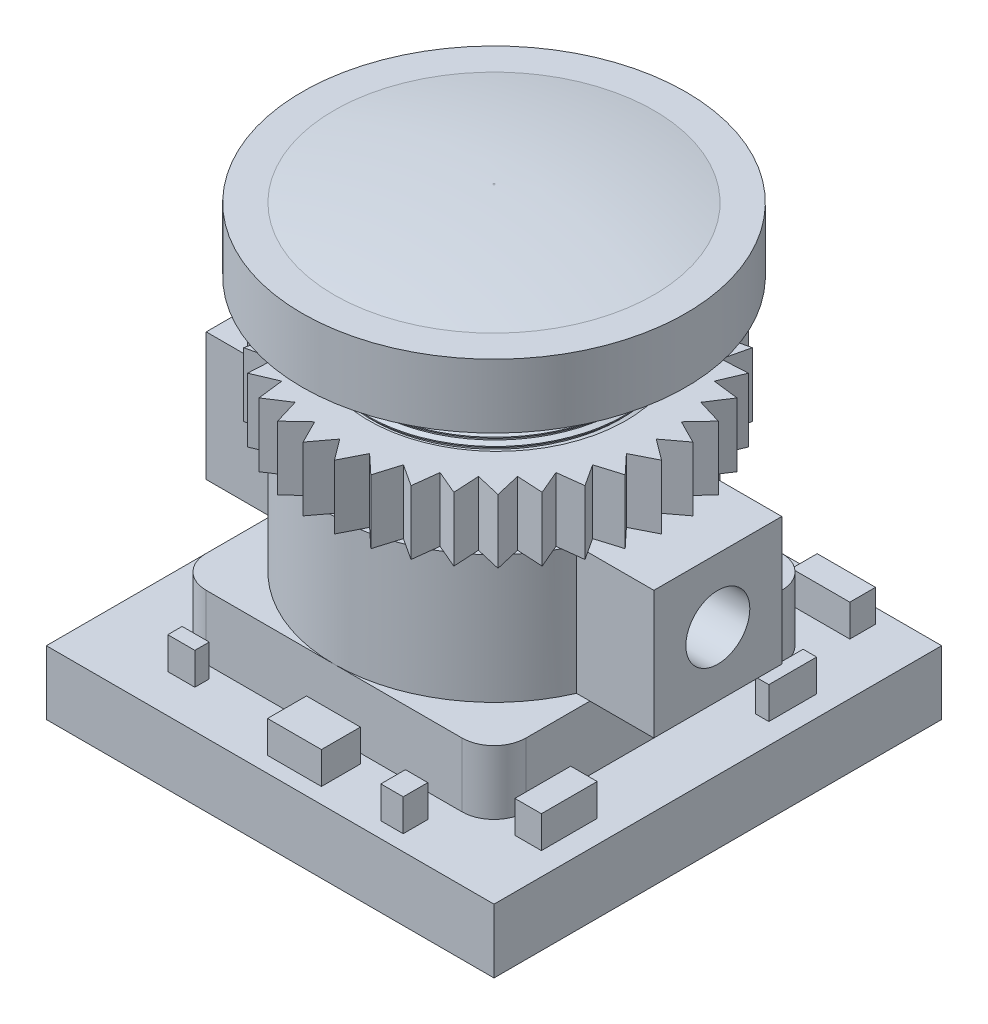
SolidWorks part; units mm, degrees
ref_plane "Front Plane" through (0, 0, 0) normal (0, 0, 1) x (1, 0, 0)
ref_plane "Top Plane" through (0, 0, 0) normal (0, 1, 0) x (1, 0, 0)
ref_plane "Right Plane" through (0, 0, 0) normal (1, 0, 0) x (0, 0, -1)
sketch "Sketch1" plane through (0, 0, 0) normal (0, 1, 0) x (1, 0, 0)
  line L1 (0, 0) -> (14, 0)
  line L2 (0, 0) -> (0, 14)
  line L3 (0, 14) -> (14, 14)
  line L4 (14, 0) -> (14, 14)
  dimension "D1" = 14
  dimension "D2" = 14
extrude "Boss-Extrude1" add sketch "Sketch1" along normal blind 2
sketch "Sketch2" plane through (0, 2, 0) normal (0, 1, 0) x (1, 0, 0)
  line L0 (0, 0) -> (14, 0) construction
  line L1 (2, 2) -> (12, 2)
  line L2 (2, 2) -> (2, 12)
  line L3 (2, 12) -> (12, 12)
  line L4 (12, 2) -> (12, 12)
  line L5 (2.4541, 13.3046) -> (3.448, 13.3046)
  line L6 (2.4541, 13.3046) -> (2.4541, 12.7429)
  line L7 (2.4541, 12.7429) -> (3.448, 12.7429)
  line L8 (3.448, 13.3046) -> (3.448, 12.7429)
  line L9 (12.3842, 12.7429) -> (10.5607, 12.7429)
  line L10 (12.3842, 12.7429) -> (12.3842, 13.5466)
  line L11 (12.3842, 13.5466) -> (10.5607, 13.5466)
  line L12 (10.5607, 12.7429) -> (10.5607, 13.5466)
  line L13 (12.9287, 10.7378) -> (13.3521, 10.7378)
  line L14 (12.9287, 10.7378) -> (12.9287, 9.2427)
  line L15 (12.9287, 9.2427) -> (13.3521, 9.2427)
  line L16 (13.3521, 10.7378) -> (13.3521, 9.2427)
  line L21 (13.2916, 2.1905) -> (12.462, 2.1905)
  line L22 (13.2916, 2.1905) -> (13.2916, 3.9363)
  line L23 (13.2916, 3.9363) -> (12.462, 3.9363)
  line L24 (12.462, 2.1905) -> (12.462, 3.9363)
  line L25 (9.973, 1.2571) -> (10.673, 1.2571)
  line L26 (9.973, 1.2571) -> (9.973, 0.488)
  line L27 (9.973, 0.488) -> (10.673, 0.488)
  line L28 (10.673, 1.2571) -> (10.673, 0.488)
  line L29 (8.1149, 0.488) -> (6.4296, 0.488)
  line L30 (8.1149, 0.488) -> (8.1149, 1.7066)
  line L31 (8.1149, 1.7066) -> (6.4296, 1.7066)
  line L32 (6.4296, 0.488) -> (6.4296, 1.7066)
  line L33 (3.448, 1.1967) -> (2.601, 1.1967)
  line L34 (3.448, 1.1967) -> (3.448, 1.6461)
  line L35 (3.448, 1.6461) -> (2.601, 1.6461)
  line L36 (2.601, 1.1967) -> (2.601, 1.6461)
  line L37 (1.0108, 5.0425) -> (1.3133, 5.0425)
  line L38 (1.0108, 5.0425) -> (1.0108, 3.7894)
  line L39 (1.0108, 3.7894) -> (1.3133, 3.7894)
  line L40 (1.3133, 5.0425) -> (1.3133, 3.7894)
  line L41 (1.659, 6.4166) -> (0.6824, 6.4166)
  line L42 (1.659, 6.4166) -> (1.659, 7.7303)
  line L43 (1.659, 7.7303) -> (0.6824, 7.7303)
  line L44 (0.6824, 6.4166) -> (0.6824, 7.7303)
  line L45 (0.9503, 10.7378) -> (1.659, 10.7378)
  line L46 (0.9503, 10.7378) -> (0.9503, 9.8736)
  line L47 (0.9503, 9.8736) -> (1.659, 9.8736)
  line L48 (1.659, 10.7378) -> (1.659, 9.8736)
  line L49 (1.4948, 12.0428) -> (0.838, 12.0428)
  line L50 (1.4948, 12.0428) -> (1.4948, 12.7429)
  line L51 (1.4948, 12.7429) -> (0.838, 12.7429)
  line L52 (0.838, 12.0428) -> (0.838, 12.7429)
  line L53 (5.8333, 13.0799) -> (6.1444, 13.0799)
  line L54 (5.8333, 13.0799) -> (5.8333, 12.5268)
  line L55 (5.8333, 12.5268) -> (6.1444, 12.5268)
  line L56 (6.1444, 13.0799) -> (6.1444, 12.5268)
  line L57 (8.2704, 12.1811) -> (6.7321, 12.1811)
  line L58 (8.2704, 12.1811) -> (8.2704, 13.7626)
  line L59 (8.2704, 13.7626) -> (6.7321, 13.7626)
  line L60 (6.7321, 12.1811) -> (6.7321, 13.7626)
  dimension "D1" = 10
  dimension "D2" = 10
  dimension "D3" = 2
  dimension "D5" = 1.3136
extrude "Boss-Extrude3" add sketch "Sketch2" along normal blind 2 contours L2 L1 L4 L3
fillet "Fillet1" radius 1 1 edges at (2, 3, -2)
fillet "Fillet2" radius 1 3 edges at (12, 3, -2) (12, 3, -12) (2, 3, -12)
sketch "Sketch4" plane through (0, 2, 0) normal (0, 1, 0) x (1, 0, 0)
  line L0 (0.9503, 9.8736) -> (1.659, 9.8736) construction
  line L1 (1.659, 10.7378) -> (1.659, 9.8736) construction
  line L2 (0.9503, 10.7378) -> (1.659, 10.7378) construction
  line L3 (0.9503, 10.7378) -> (0.9503, 9.8736) construction
  line L4 (1.659, 6.4166) -> (0.6824, 6.4166) construction
  line L5 (0.6824, 6.4166) -> (0.6824, 7.7303) construction
  line L6 (1.659, 7.7303) -> (0.6824, 7.7303) construction
  line L7 (1.659, 6.4166) -> (1.659, 7.7303) construction
  line L8 (1.0108, 3.7894) -> (1.3133, 3.7894) construction
  line L9 (1.3133, 5.0425) -> (1.3133, 3.7894) construction
  line L10 (1.0108, 5.0425) -> (1.3133, 5.0425) construction
  line L11 (1.0108, 5.0425) -> (1.0108, 3.7894) construction
  line L12 (3.448, 1.6461) -> (2.601, 1.6461) construction
  line L13 (2.601, 1.1967) -> (2.601, 1.6461) construction
  line L14 (3.448, 1.1967) -> (2.601, 1.1967) construction
  line L15 (3.448, 1.1967) -> (3.448, 1.6461) construction
  line L16 (8.1149, 1.7066) -> (6.4296, 1.7066) construction
  line L17 (6.4296, 0.488) -> (6.4296, 1.7066) construction
  line L18 (8.1149, 0.488) -> (6.4296, 0.488) construction
  line L19 (8.1149, 0.488) -> (8.1149, 1.7066) construction
  line L20 (9.973, 1.2571) -> (10.673, 1.2571) construction
  line L21 (10.673, 1.2571) -> (10.673, 0.488) construction
  line L22 (9.973, 0.488) -> (10.673, 0.488) construction
  line L23 (9.973, 1.2571) -> (9.973, 0.488) construction
  line L24 (13.2916, 3.9363) -> (12.462, 3.9363) construction
  line L25 (12.462, 2.1905) -> (12.462, 3.9363) construction
  line L26 (13.2916, 2.1905) -> (12.462, 2.1905) construction
  line L27 (13.2916, 2.1905) -> (13.2916, 3.9363) construction
  line L28 (12.9287, 10.7378) -> (12.9287, 9.2427) construction
  line L29 (12.9287, 9.2427) -> (13.3521, 9.2427) construction
  line L30 (13.3521, 10.7378) -> (13.3521, 9.2427) construction
  line L31 (12.9287, 10.7378) -> (13.3521, 10.7378) construction
  line L32 (10.5607, 12.7429) -> (10.5607, 13.5466) construction
  line L33 (12.3842, 13.5466) -> (10.5607, 13.5466) construction
  line L34 (12.3842, 12.7429) -> (12.3842, 13.5466) construction
  line L35 (12.3842, 12.7429) -> (10.5607, 12.7429) construction
  line L36 (6.7321, 12.1811) -> (6.7321, 13.7626) construction
  line L37 (8.2704, 13.7626) -> (6.7321, 13.7626) construction
  line L38 (8.2704, 12.1811) -> (8.2704, 13.7626) construction
  line L39 (8.2704, 12.1811) -> (6.7321, 12.1811) construction
  line L40 (5.8333, 13.0799) -> (5.8333, 12.5268) construction
  line L41 (5.8333, 12.5268) -> (6.1444, 12.5268) construction
  line L42 (6.1444, 13.0799) -> (6.1444, 12.5268) construction
  line L43 (5.8333, 13.0799) -> (6.1444, 13.0799) construction
  line L44 (2.4541, 13.3046) -> (2.4541, 12.7429) construction
  line L45 (2.4541, 12.7429) -> (3.448, 12.7429) construction
  line L46 (3.448, 13.3046) -> (3.448, 12.7429) construction
  line L47 (2.4541, 13.3046) -> (3.448, 13.3046) construction
  line L48 (1.4948, 12.7429) -> (0.838, 12.7429) construction
  line L49 (0.838, 12.0428) -> (0.838, 12.7429) construction
  line L50 (1.4948, 12.0428) -> (0.838, 12.0428) construction
  line L51 (1.4948, 12.0428) -> (1.4948, 12.7429) construction
  line L52 (0.9503, 9.8736) -> (1.659, 9.8736)
  line L53 (1.659, 10.7378) -> (1.659, 9.8736)
  line L54 (0.9503, 10.7378) -> (1.659, 10.7378)
  line L55 (0.9503, 10.7378) -> (0.9503, 9.8736)
  line L56 (1.659, 6.4166) -> (0.6824, 6.4166)
  line L57 (0.6824, 6.4166) -> (0.6824, 7.7303)
  line L58 (1.659, 7.7303) -> (0.6824, 7.7303)
  line L59 (1.659, 6.4166) -> (1.659, 7.7303)
  line L60 (1.0108, 3.7894) -> (1.3133, 3.7894)
  line L61 (1.3133, 5.0425) -> (1.3133, 3.7894)
  line L62 (1.0108, 5.0425) -> (1.3133, 5.0425)
  line L63 (1.0108, 5.0425) -> (1.0108, 3.7894)
  line L64 (3.448, 1.6461) -> (2.601, 1.6461)
  line L65 (2.601, 1.1967) -> (2.601, 1.6461)
  line L66 (3.448, 1.1967) -> (2.601, 1.1967)
  line L67 (3.448, 1.1967) -> (3.448, 1.6461)
  line L68 (8.1149, 1.7066) -> (6.4296, 1.7066)
  line L69 (6.4296, 0.488) -> (6.4296, 1.7066)
  line L70 (8.1149, 0.488) -> (6.4296, 0.488)
  line L71 (8.1149, 0.488) -> (8.1149, 1.7066)
  line L72 (9.973, 1.2571) -> (10.673, 1.2571)
  line L73 (10.673, 1.2571) -> (10.673, 0.488)
  line L74 (9.973, 0.488) -> (10.673, 0.488)
  line L75 (9.973, 1.2571) -> (9.973, 0.488)
  line L76 (13.2916, 3.9363) -> (12.462, 3.9363)
  line L77 (12.462, 2.1905) -> (12.462, 3.9363)
  line L78 (13.2916, 2.1905) -> (12.462, 2.1905)
  line L79 (13.2916, 2.1905) -> (13.2916, 3.9363)
  line L80 (12.9287, 10.7378) -> (12.9287, 9.2427)
  line L81 (12.9287, 9.2427) -> (13.3521, 9.2427)
  line L82 (13.3521, 10.7378) -> (13.3521, 9.2427)
  line L83 (12.9287, 10.7378) -> (13.3521, 10.7378)
  line L84 (10.5607, 12.7429) -> (10.5607, 13.5466)
  line L85 (12.3842, 13.5466) -> (10.5607, 13.5466)
  line L86 (12.3842, 12.7429) -> (12.3842, 13.5466)
  line L87 (12.3842, 12.7429) -> (10.5607, 12.7429)
  line L88 (6.7321, 12.1811) -> (6.7321, 13.7626)
  line L89 (8.2704, 13.7626) -> (6.7321, 13.7626)
  line L90 (8.2704, 12.1811) -> (8.2704, 13.7626)
  line L91 (8.2704, 12.1811) -> (6.7321, 12.1811)
  line L92 (5.8333, 13.0799) -> (5.8333, 12.5268)
  line L93 (5.8333, 12.5268) -> (6.1444, 12.5268)
  line L94 (6.1444, 13.0799) -> (6.1444, 12.5268)
  line L95 (5.8333, 13.0799) -> (6.1444, 13.0799)
  line L96 (2.4541, 13.3046) -> (2.4541, 12.7429)
  line L97 (2.4541, 12.7429) -> (3.448, 12.7429)
  line L98 (3.448, 13.3046) -> (3.448, 12.7429)
  line L99 (2.4541, 13.3046) -> (3.448, 13.3046)
  line L100 (1.4948, 12.7429) -> (0.838, 12.7429)
  line L101 (0.838, 12.0428) -> (0.838, 12.7429)
  line L102 (1.4948, 12.0428) -> (0.838, 12.0428)
  line L103 (1.4948, 12.0428) -> (1.4948, 12.7429)
extrude "Boss-Extrude4" add sketch "Sketch4" along normal blind 1
sketch "Sketch5" plane through (0, 4, 0) normal (0, 1, 0) x (1, 0, 0)
  line L0 (2, 2) -> (12, 2) construction
  line L1 (12, 2) -> (12, 12) construction
  circle A0 centre (7, 7) radius 5
  dimension "D1" = 10
  dimension "D2" = 5
  dimension "D3" = 5
extrude "Boss-Extrude5" add sketch "Sketch5" along normal blind 4
sketch "Sketch7" plane through (0, 4, 0) normal (0, 1, 0) x (1, 0, 0)
  line L0 (2, 2) -> (2, 12) construction
  line L1 (4, 5) -> (0, 5)
  line L2 (4, 5) -> (4, 9)
  line L3 (4, 9) -> (0, 9)
  line L4 (0, 5) -> (0, 9)
  line L5 (4, 5) -> (0, 9) construction
  line L6 (4, 9) -> (0, 5) construction
  line L7 (0, 14) -> (0, 0) construction
  line L9 (14, 5) -> (10, 5)
  line L10 (14, 5) -> (14, 9)
  line L11 (14, 9) -> (10, 9)
  line L12 (10, 5) -> (10, 9)
  line L13 (14, 5) -> (10, 9) construction
  line L14 (14, 9) -> (10, 5) construction
  line L15 (12, 2) -> (12, 12) construction
  point P0 (2, 7)
  point P10 (12, 7)
  point P27 (6.9741, 7)
extrude "Boss-Extrude9" add sketch "Sketch7" along normal blind 4
sketch "Sketch8" plane through (0, 8, 0) normal (0, 1, 0) x (1, 0, 0)
  line L72 (3.8094, 3.3424) -> (3.7648, 2.5266)
  line L73 (3.7648, 2.5266) -> (4.5161, 2.8475)
  line L74 (4.5161, 2.8475) -> (4.6139, 2.0364)
  line L75 (4.6139, 2.0364) -> (5.2981, 2.4829)
  line L76 (5.2981, 2.4829) -> (5.5352, 1.7011)
  line L77 (5.5352, 1.7011) -> (6.1315, 2.2596)
  line L78 (6.1315, 2.2596) -> (6.5008, 1.5308)
  line L79 (6.5008, 1.5308) -> (6.991, 2.1844)
  line L80 (6.991, 2.1844) -> (7.4813, 1.5308)
  line L81 (7.4813, 1.5308) -> (7.8506, 2.2596)
  line L82 (7.8506, 2.2596) -> (8.4468, 1.7011)
  line L83 (8.4468, 1.7011) -> (8.684, 2.4829)
  line L84 (8.684, 2.4829) -> (9.3682, 2.0364)
  line L85 (9.3682, 2.0364) -> (9.4659, 2.8475)
  line L86 (9.4659, 2.8475) -> (10.2173, 2.5266)
  line L87 (10.2173, 2.5266) -> (10.1727, 3.3424)
  line L88 (10.1727, 3.3424) -> (10.9683, 3.1569)
  line L89 (10.9683, 3.1569) -> (10.7828, 3.9525)
  line L90 (10.7828, 3.9525) -> (11.5986, 3.908)
  line L91 (11.5986, 3.908) -> (11.2777, 4.6593)
  line L92 (11.2777, 4.6593) -> (12.0888, 4.7571)
  line L93 (12.0888, 4.7571) -> (11.6423, 5.4413)
  line L94 (11.6423, 5.4413) -> (12.4241, 5.6784)
  line L95 (12.4241, 5.6784) -> (11.8656, 6.2747)
  line L96 (11.8656, 6.2747) -> (12.5944, 6.644)
  line L97 (12.5944, 6.644) -> (11.9408, 7.1342)
  line L98 (11.9408, 7.1342) -> (12.5944, 7.6244)
  line L99 (12.5944, 7.6244) -> (11.8656, 7.9937)
  line L100 (11.8656, 7.9937) -> (12.4241, 8.59)
  line L101 (12.4241, 8.59) -> (11.6423, 8.8271)
  line L102 (11.6423, 8.8271) -> (12.0888, 9.5113)
  line L103 (12.0888, 9.5113) -> (11.2777, 9.6091)
  line L104 (11.2777, 9.6091) -> (11.5986, 10.3604)
  line L105 (11.5986, 10.3604) -> (10.7828, 10.3159)
  line L106 (10.7828, 10.3159) -> (10.9683, 11.1115)
  line L107 (10.9683, 11.1115) -> (10.1727, 10.926)
  line L108 (10.1727, 10.926) -> (10.2173, 11.7417)
  line L109 (10.2173, 11.7417) -> (9.4659, 11.4208)
  line L110 (9.4659, 11.4208) -> (9.3682, 12.232)
  line L111 (9.3682, 12.232) -> (8.684, 11.7855)
  line L112 (8.684, 11.7855) -> (8.4468, 12.5673)
  line L113 (8.4468, 12.5673) -> (7.8506, 12.0088)
  line L114 (7.8506, 12.0088) -> (7.4813, 12.7376)
  line L115 (7.4813, 12.7376) -> (6.991, 12.084)
  line L116 (6.991, 12.084) -> (6.5008, 12.7376)
  line L117 (6.5008, 12.7376) -> (6.1315, 12.0088)
  line L118 (6.1315, 12.0088) -> (5.5352, 12.5673)
  line L119 (5.5352, 12.5673) -> (5.2981, 11.7855)
  line L120 (5.2981, 11.7855) -> (4.6139, 12.232)
  line L121 (4.6139, 12.232) -> (4.5161, 11.4208)
  line L122 (4.5161, 11.4208) -> (3.7648, 11.7417)
  line L123 (3.7648, 11.7417) -> (3.8094, 10.926)
  line L124 (3.8094, 10.926) -> (3.0137, 11.1115)
  line L125 (3.0137, 11.1115) -> (3.1993, 10.3159)
  line L126 (3.1993, 10.3159) -> (2.3835, 10.3604)
  line L127 (2.3835, 10.3604) -> (2.7044, 9.6091)
  line L128 (2.7044, 9.6091) -> (1.8933, 9.5113)
  line L129 (1.8933, 9.5113) -> (2.3397, 8.8271)
  line L130 (2.3397, 8.8271) -> (1.5579, 8.59)
  line L131 (1.5579, 8.59) -> (2.1164, 7.9937)
  line L132 (2.1164, 7.9937) -> (1.3877, 7.6244)
  line L133 (1.3877, 7.6244) -> (2.0412, 7.1342)
  line L134 (2.0412, 7.1342) -> (1.3877, 6.644)
  line L135 (1.3877, 6.644) -> (2.1164, 6.2747)
  line L136 (2.1164, 6.2747) -> (1.5579, 5.6784)
  line L137 (1.5579, 5.6784) -> (2.3397, 5.4413)
  line L138 (2.3397, 5.4413) -> (1.8933, 4.7571)
  line L139 (1.8933, 4.7571) -> (2.7044, 4.6593)
  line L140 (2.7044, 4.6593) -> (2.3835, 3.908)
  line L141 (2.3835, 3.908) -> (3.1993, 3.9525)
  line L142 (3.1993, 3.9525) -> (3.0137, 3.1569)
  line L143 (3.0137, 3.1569) -> (3.8094, 3.3424)
extrude "Boss-Extrude10" add sketch "Sketch8" along normal blind 2
sketch "Sketch9" plane through (0, 10, 0) normal (0, 1, 0) x (1, 0, 0)
  circle A0 centre (6.9481, 7.1599) radius 4.0216
  point P2 (0, 0)
  point P3 (6.9481, 7.1599)
extrude "Boss-Extrude11" add sketch "Sketch9" along normal blind 2
thread "Thread1" pitch 0.25 method cut profile "Thread Profile1" start angle 13, offset 0.0001, length 2, pitch 0.25, diameter 8.0433
ref_plane "Plane1" through (3.0296, 11.9999, -8.0646) normal (-0.225, 0, 0.9744) x (-0.9744, 0, -0.225)
sketch "Thread Profile1" plane through (3.0296, 11.9999, -8.0646) normal (-0.225, 0, 0.9744) x (-0.9744, 0, -0.225)
  line L0 (0, 0) -> (0, 0.25) construction
  line L11 (0, 0) -> (0, 0.2187)
  line L12 (0, 0.2187) -> (-0.1353, 0.1406)
  line L13 (-0.1353, 0.1406) -> (-0.1353, 0.0781)
  line L15 (-0.1353, 0.0781) -> (0, 0)
  line L17 (-0.1353, 0.1094) -> (0, 0.1094) construction
  point P2 (0, 0)
  dimension "Pitch" = 0.25
  dimension "Profile_Angle" = 60
  dimension "Profile_Land" = 0.0625
  dimension "Profile_Height" = 0.1353
sketch "Sketch14" plane through (0, 12, 0) normal (0, 1, 0) x (1, 0, 0)
  arc A0 (2.4174, 5) -> (7, 2) centre (7, 7) ccw construction
  arc A1 (7, 12) -> (2.4174, 9) centre (7, 7) ccw construction
  arc A4 (2.4174, 5) -> (7, 2) centre (7, 7) ccw
  arc A5 (7, 12) -> (2.4174, 9) centre (7, 7) ccw
  circle A8 centre (7, 7) radius 6
  dimension "D1" = 12
extrude "Boss-Extrude12" add sketch "Sketch14" along normal blind 2
sketch "Sketch20" plane through (0, 0, 0) normal (-1, 0, 0) x (0, 0, 1)
  line L0 (-5, 8) -> (-9, 8) construction
  line L1 (-9, 8) -> (-9, 4) construction
  circle A0 centre (-7, 6) radius 1
  dimension "D1" = 2
  dimension "D2" = 2
  dimension "D3" = 2
extrude "Cut-Extrude1" cut sketch "Sketch20" against normal blind 2
sketch "Sketch21" plane through (14, 0, 0) normal (1, 0, 0) x (0, 0, -1)
  line L0 (5, 8) -> (9, 8) construction
  line L1 (5, 8) -> (5, 4) construction
  circle A0 centre (7, 6) radius 1
  dimension "D1" = 2
  dimension "D2" = 2
  dimension "D3" = 2
extrude "Cut-Extrude2" cut sketch "Sketch21" against normal blind 2
sketch "Sketch22" plane through (0, 14, 0) normal (0, 1, 0) x (1, 0, 0)
  line L0 (14, 14) -> (0, 14) construction
  line L1 (0, 5) -> (0, 9) construction
  circle A0 centre (7, 7) radius 5
  dimension "D1" = 10
  dimension "D2" = 7
  dimension "D3" = 7
extrude "Boss-Extrude13" add sketch "Sketch22" along normal blind 0.5
fillet "Fillet3" radius 25 1 edges at (7, 14.5, -2)
sketch "Sketch17" plane through (0, 14, 0) normal (0, 1, 0) x (1, 0, 0)
  line L0 (0, 7) -> (14, 7)
  line L1 (0, 5) -> (0, 9) construction
  line L2 (14, 0) -> (14, 14) construction
